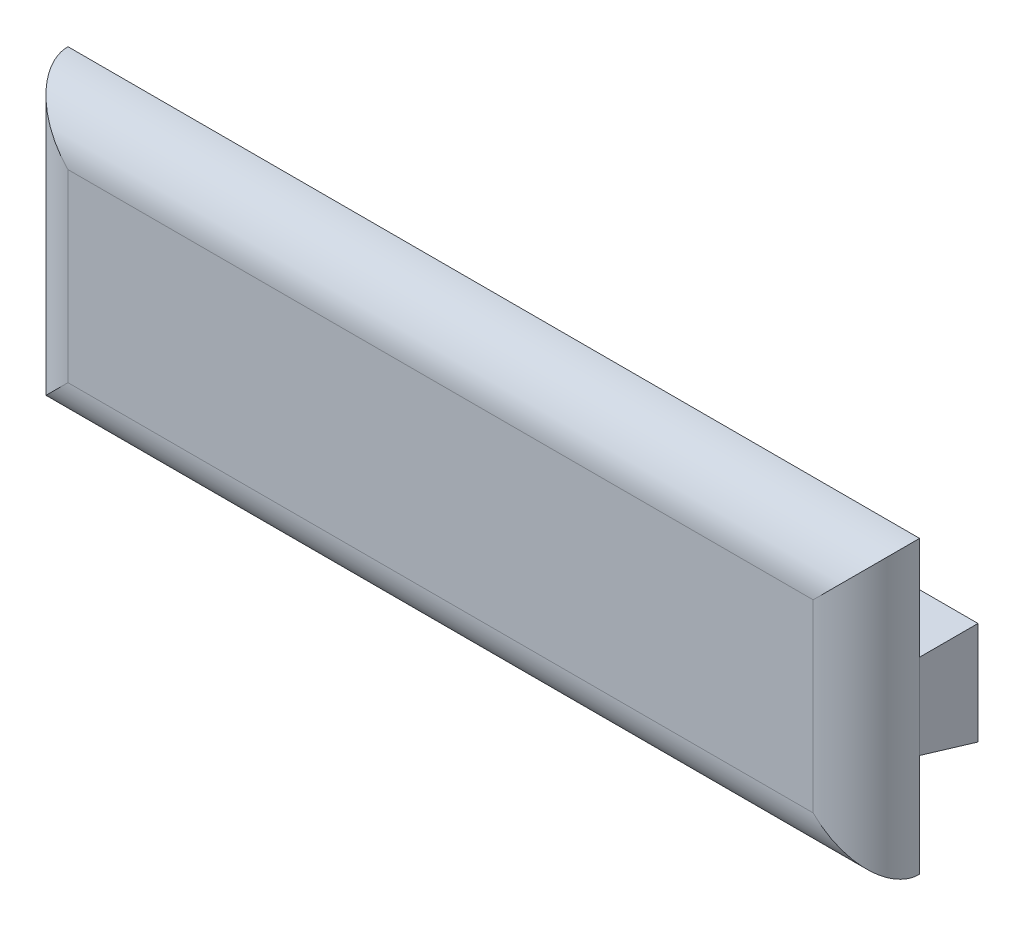
SolidWorks part; units mm, degrees
ref_plane "Front Plane" through (0, 0, 0) normal (0, 0, 1) x (1, 0, 0)
ref_plane "Top Plane" through (0, 0, 0) normal (0, 1, 0) x (1, 0, 0)
ref_plane "Right Plane" through (0, 0, 0) normal (1, 0, 0) x (0, 0, -1)
sketch "Sketch1" plane through (0, 0, 0) normal (0, 0, 1) x (1, 0, 0)
  line L1 (-12, -4.1) -> (12, -4.1)
  line L2 (-12, -4.1) -> (-12, 4.1)
  line L3 (-12, 4.1) -> (12, 4.1)
  line L4 (12, -4.1) -> (12, 4.1)
  line L5 (-12, -4.1) -> (12, 4.1) construction
  line L6 (-12, 4.1) -> (12, -4.1) construction
  point P0 (0, 0)
  dimension "D1" = 24
  dimension "D2" = 8.2
extrude "Boss-Extrude1" add sketch "Sketch1" along normal blind 1.5
sketch "Sketch2" plane through (0, 0, 0) normal (0, 0, -1) x (-1, 0, 0)
  line L0 (-12, -4.1) -> (-12, 4.1) construction
  line L1 (-12, 1.2) -> (12, 1.2)
  line L2 (-12, 1.2) -> (-12, -1.2)
  line L3 (-12, -1.2) -> (12, -1.2)
  line L4 (12, 1.2) -> (12, -1.2)
  line L5 (12, 4.1) -> (12, -4.1) construction
  line L6 (-12, 4.1) -> (0, 1.2) construction
  line L7 (-12, -4.1) -> (0, -1.2) construction
  dimension "D1" = 2.4
extrude "Boss-Extrude2" add sketch "Sketch2" along normal blind 1.4 draft 10 draft outward yes
fillet "Fillet1" radius 1.5 4 edges at (0, -4.1, 1.5) (-12, 0, 1.5) (0, 4.1, 1.5) (12, 0, 1.5)
